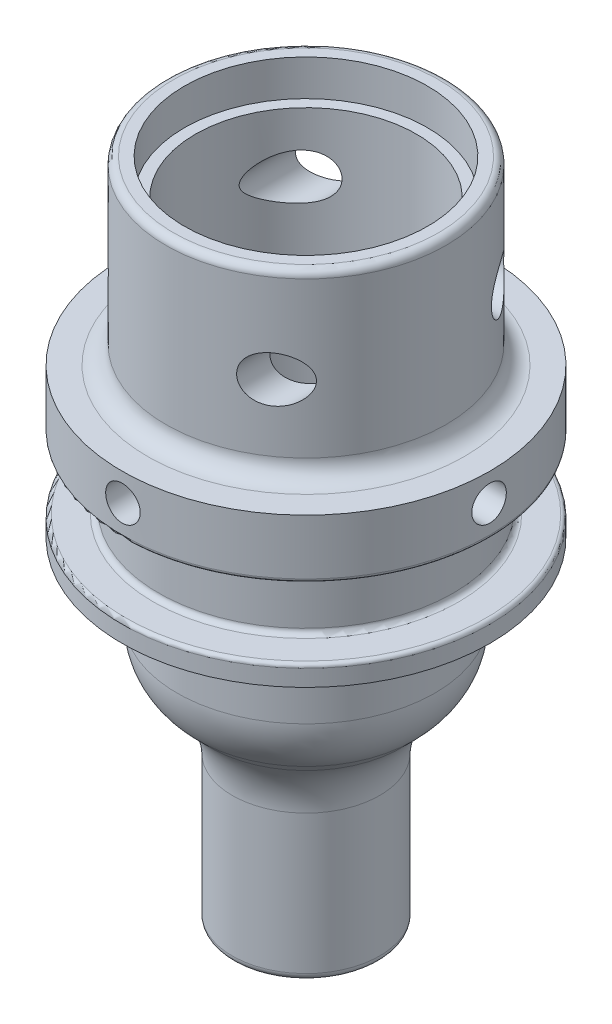
SolidWorks part; units mm, degrees
material "Brass"
ref_plane "Front Plane" through (0, 0, 0) normal (0, 0, 1) x (1, 0, 0)
ref_plane "Top Plane" through (0, 0, 0) normal (0, 1, 0) x (1, 0, 0)
ref_plane "Right Plane" through (0, 0, 0) normal (1, 0, 0) x (0, 0, -1)
sketch "Sketch1" plane through (0, 0, 0) normal (0, 0, 1) x (1, 0, 0)
  line L0 (4.826, 22.86) -> (4.826, 16.6243)
  line L2 (6.3373, 15.2908) -> (6.3373, 14.7193)
  line L3 (6.3373, 11.4808) -> (5.0673, 11.4808)
  line L5 (4.445, 8.001) -> (2.54, 6.096)
  line L6 (2.54, 6.096) -> (2.54, 0)
  line L7 (2.54, 0) -> (1.905, 0)
  line L8 (1.905, 0) -> (1.905, 6.8564)
  line L9 (1.905, 6.8564) -> (3.81, 8.001)
  line L10 (3.81, 8.001) -> (3.81, 21.6154)
  line L11 (4.191, 22.86) -> (4.826, 22.86)
  line L12 (0, 20.955) -> (0, 0) construction
  line L13 (6.2103, 14.5923) -> (5.2578, 14.5923)
  line L14 (5.08, 14.4145) -> (5.08, 12.3571)
  line L15 (5.2578, 12.1793) -> (6.2103, 12.1793)
  line L16 (5.08, 11.4808) -> (5.08, 15.2908) construction
  line L17 (6.3373, 12.0523) -> (6.3373, 11.4808)
  line L18 (5.0673, 11.4808) -> (4.445, 11.4808)
  line L19 (4.445, 11.4808) -> (4.445, 8.001)
  line L20 (6.3373, 15.2908) -> (6.3373, 16.6243)
  line L21 (6.3373, 16.6243) -> (4.826, 16.6243)
  line L22 (4.191, 22.86) -> (4.191, 21.6154)
  line L23 (4.191, 21.6154) -> (3.81, 21.6154)
  arc A0 (6.2103, 12.1793) -> (6.3373, 12.0523) centre (6.2103, 12.0523) cw
  arc A1 (6.2103, 14.5923) -> (6.3373, 14.7193) centre (6.2103, 14.7193) ccw
  arc A2 (5.08, 12.3571) -> (5.2578, 12.1793) centre (5.2578, 12.3571) ccw
  arc A3 (5.2578, 14.5923) -> (5.08, 14.4145) centre (5.2578, 14.4145) ccw
  point P1 (0, 0)
  point P20 (5.08, 13.3858)
  point P36 (6.3373, 12.1793)
  point P41 (5.08, 12.1793)
  point P44 (5.08, 14.5923)
  dimension "D14" = 0.127
  dimension "D15" = 0.1778
  dimension "D1" = 6.3373
  dimension "D3" = 0.6985
  dimension "D4" = 6.096
  dimension "D5" = 0.635
  dimension "D6" = 59
  dimension "D7" = 11.3792
  dimension "D8" = 2.54
  dimension "D9" = 1.27
  dimension "D10" = 2.413
  dimension "D11" = 5.08
  dimension "D12" = 0.635
  dimension "D13" = 135
  dimension "D16" = 20.955
  dimension "D17" = 1.016
  dimension "D18" = 3.81
  dimension "D19" = 2.032
  dimension "D20" = 1.2446
  dimension "D21" = 0.381
  dimension "D22" = 22.86
revolve "Revolve1" add sketch "Sketch1" angle 360 about L12
sketch "Sketch2" plane through (0, 0, 0) normal (0, 0, 1) x (1, 0, 0)
  line L0 (3.81, 22.86) -> (-3.81, 22.86) construction
  point P0 (2.794, 19.558)
  dimension "D1" = 3.302
  dimension "D2" = 2.794
hole_wizard "1/16 (0.0625) Diameter Hole1" positions "Sketch2" profile "Sketch3" hole size "1/16" standard "ANSI Inch" end condition through all
sketch "Sketch3" plane through (2.794, 19.558, 0) normal (1, 0, 0) x (0, 1, 0)
  line L0 (0, 0) -> (0, 6.3373)
  line L1 (0, 6.3373) -> (0.7937, 6.3373)
  line L2 (0.7937, 6.3373) -> (0.7937, 0)
  line L5 (0.7937, 0) -> (0, 0)
  line L11 (0, -6.35) -> (0, 107.95) construction
  dimension "Thru Hole Dia." = 1.5875
  dimension "Thru Hole Depth" = 6.3373
pattern_circular "CirPattern1" count 4 over 360 about axis through (0, 20.955, 0) along (0, 1, 0) of "1/16 (0.0625) Diameter Hole1" reverse direction yes
ref_plane "Plane1" through (0, 0, 6.3373) normal (0, 0, 1) x (1, 0, 0)
sketch "Sketch5" plane through (0, 0, 6.3373) normal (0, 0, 1) x (1, 0, 0)
  line L0 (0, 14.7193) -> (0, 16.6243) construction
  line L1 (6.3373, 16.6243) -> (-6.3373, 16.6243) construction
  line L2 (-6.3373, 14.7193) -> (6.3373, 14.7193) construction
  point P0 (0, 15.6718)
  point P8 (0, 15.6718)
hole_wizard "#0-80 Tapped Hole1" positions "Sketch5" profile "Sketch7" tap size "#0-80" standard "ANSI Inch"
sketch "Sketch7" plane through (0, 15.6718, 6.3373) normal (1, 0, 0) x (0, -1, 0)
  line L0 (0, 0) -> (0, 2.1359)
  line L1 (0, 2.1359) -> (0.5956, 1.778)
  line L2 (0.5956, 1.778) -> (0.5956, 0)
  line L5 (0.5956, 0) -> (0, 0)
  line L10 (0, 2.1359) -> (-0.5956, 1.778) construction
  line L11 (0, -6.35) -> (0, 107.95) construction
  dimension "Tap Drill Dia." = 1.1913
  dimension "Tap Drill Depth" = 1.778
  dimension "Drill Angle" = 118
cosmetic thread "Hole Thread2" parameters "D1"=1.778, "D2"=1.524
pattern_circular "CirPattern2" count 4 over 360 about axis through (0, 20.955, 0) along (0, 1, 0) of "#0-80 Tapped Hole1" reverse direction yes
cosmetic thread "Hole Thread3" parameters "D1"=1.778, "D2"=1.524
cosmetic thread "Hole Thread4" parameters "D1"=1.778, "D2"=1.524
cosmetic thread "Hole Thread5" parameters "D1"=1.778, "D2"=1.524
fillet "Fillet1" radius 0.254 1 edges at (-4.826, 22.86, 0)
fillet "Fillet2" radius 1.905 2 edges at (-3.81, 8.001, 0) (-1.905, 6.8564, 0)
fillet "Fillet3" radius 2.54 2 edges at (-4.445, 8.001, 0) (-2.54, 6.096, 0)
fillet "Fillet4" radius 0.635 1 edges at (-4.826, 16.6243, 0)
fillet "Fillet5" radius 0.254 2 edges at (-1.905, 0, 0) (-2.54, 0, 0)
